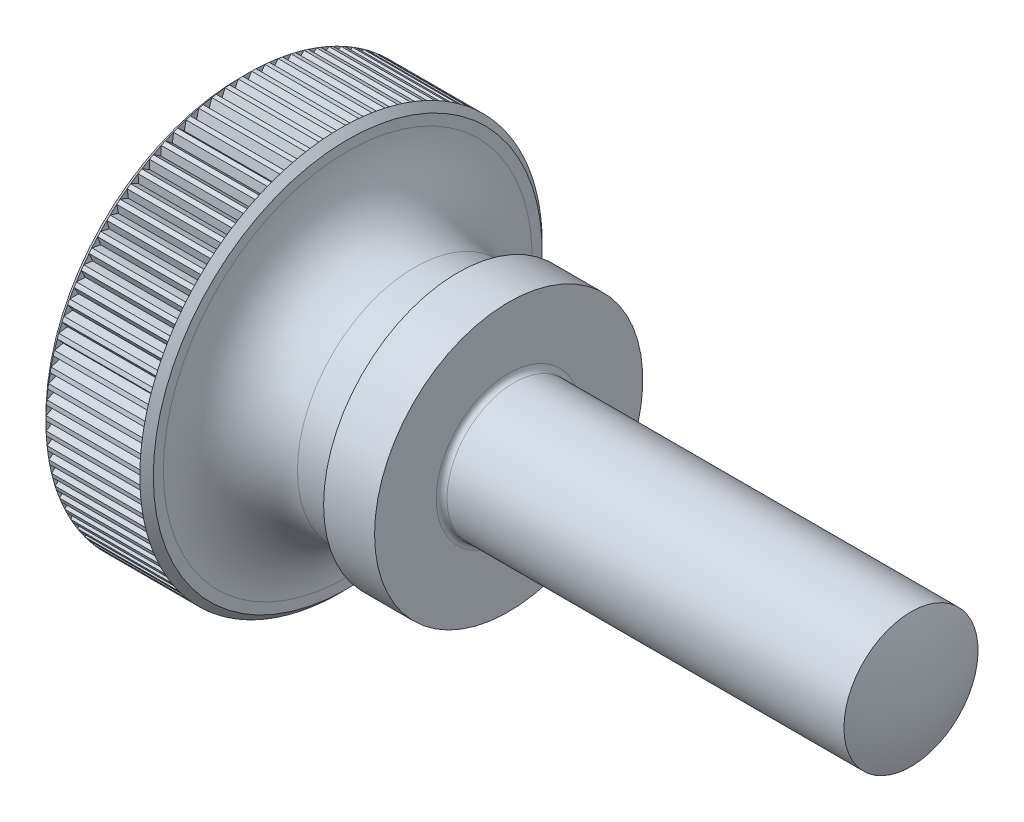
SolidWorks part; units mm, degrees
ref_plane "Front" through (0, 0, 0) normal (0, 0, 1) x (1, 0, 0)
ref_plane "Top" through (0, 0, 0) normal (0, 1, 0) x (1, 0, 0)
ref_plane "Right" through (0, 0, 0) normal (1, 0, 0) x (0, 0, -1)
sketch "Sketch1" plane through (0, 0, 0) normal (0, 0, 1) x (1, 0, 0)
  line L0 (0, 0) -> (0, 15)
  line L1 (0, 15) -> (8, 15)
  line L2 (8, 15) -> (8, 8.75)
  line L3 (8, 8.75) -> (16.2, 8.75)
  line L4 (16.2, 8.75) -> (16.2, 10)
  line L5 (16.2, 10) -> (20, 10)
  line L6 (20, 10) -> (20, 5)
  line L7 (20, 5) -> (50, 5)
  line L8 (0, 0) -> (50.9233, 0)
  line L9 (-48.2111, 0) -> (101.1311, 0) construction
  arc A0 (50.9233, 0) -> (50, 5) centre (36.9233, 0) ccw
revolve "Base" add sketch "Sketch1" angle 360 about L9
cosmetic thread "ThreadCosmetic1" [suppressed] parameters "D1"=30, "THD_MINOR"=7.5
fillet "Fillet1" radius 5 1 edges at (8, 0, 8.75)
chamfer "Chamfer1" distance 0.5 angle 45 2 edges at (8, 0, 15) (0, 0, 15)
ref_plane "Plane1" through (0.5, 0, 0) normal (-1, 0, 0) x (0, 0, 1)
sketch "Sketch2" plane through (0.5, 0, 0) normal (1, 0, 0) x (0, 0, -1)
  line L1 (0, 14.4226) -> (0.5, 15.2887)
  line L2 (0.5, 15.2887) -> (-0.5, 15.2887)
  line L3 (-0.5, 15.2887) -> (0, 14.4226)
  circle A1 centre (0, 0) radius 15 construction
  circle A2 centre (0, 15) radius 0.2887 construction
  dimension "D1" = 1
extrude "Cut-Extrude1" cut sketch "Sketch2" along normal blind 7
pattern_circular "Circular-Pattern1" count 95 over 360 about axis through (-48.2111, 0, 0) along (1, 0, 0) of "Cut-Extrude1"
fillet "Fillet2" radius 0.4 1 edges at (20, 0, 5)
sketch "Sketch3" plane through (0, 0, 0) normal (0, 0, 1) x (1, 0, 0)
  line L0 (20.4, 6.25) -> (21.65, 6.25)
  line L1 (21.65, 6.25) -> (21.65, 5)
  line L2 (21.65, 5) -> (21.025, 3.9175)
  line L3 (21.025, 3.9175) -> (20.4, 5)
  line L4 (20.4, 5) -> (20.4, 6.25)
  line L5 (20.4, -5) -> (20.4, 5) construction
  line L6 (50, 5) -> (20.4, 5) construction
  dimension "D1" = 1.25
revolve "Cut-Revolve10" [suppressed] cut sketch "Sketch3" angle 360 about axis through (-48.2111, 0, 0) along (1, 0, 0)
pattern_linear "LPattern10" [suppressed] count 20 along (1, 0, 0) of bodies 104
equation "\"D1@Circular-Pattern1\" =int (  \"dk@Sketch1\" * PI+1 )"
equation "\"D1@ThreadCosmetic1\" = \"l@Sketch1\""
equation "\"D1@Plane1\" = \"c@Chamfer1\""
equation "\"D1@Cut-Extrude1\" =\"k1@Sketch1\" - 2 * \"c@Chamfer1\""
equation "\"D1@Sketch3\" =  ( \"d@Sketch1\" - \"THD_MINOR@ThreadCosmetic1\" )  / 2"
equation "\"pitch@LPattern10\" = 1.2 * \"D1@Sketch3\""
equation "\"D1@LPattern10\" = \"D1@ThreadCosmetic1\" / \"pitch@LPattern10\""
